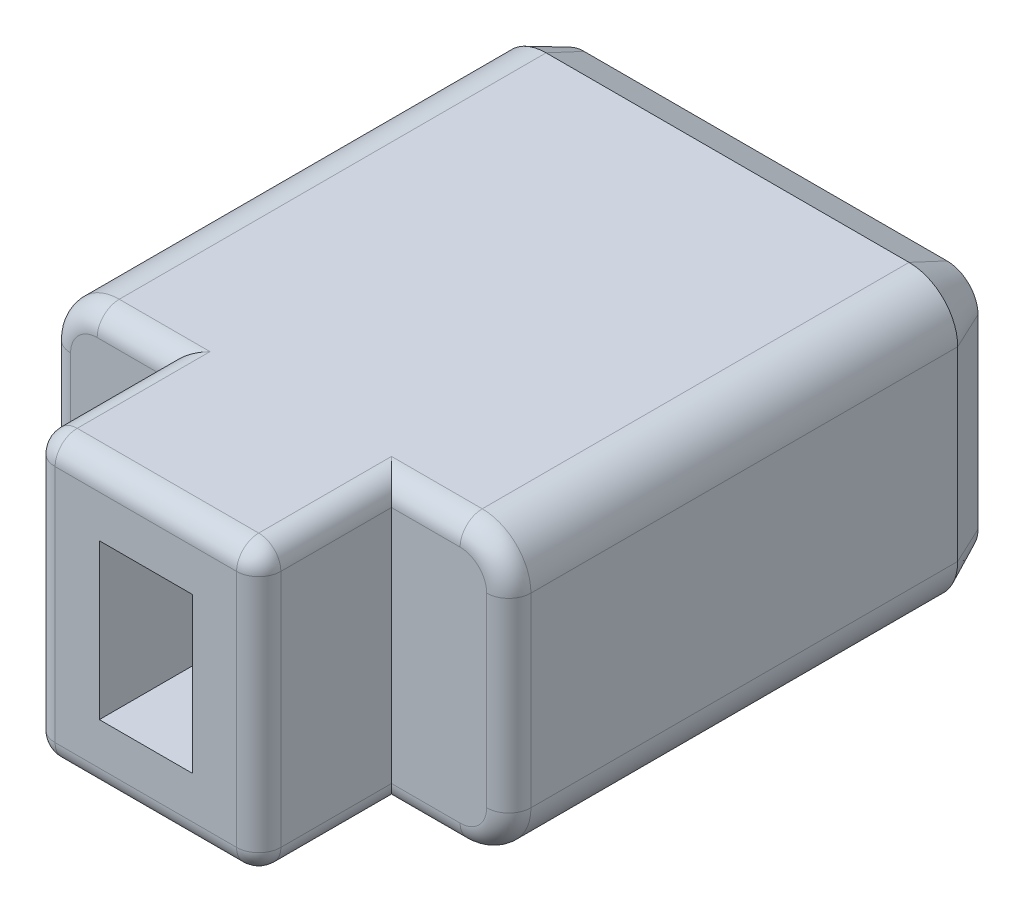
SolidWorks part; units mm, degrees
ref_plane "Plan de face" through (0, 0, 0) normal (0, 0, 1) x (1, 0, 0)
ref_plane "Plan de dessus" through (0, 0, 0) normal (0, 1, 0) x (1, 0, 0)
ref_plane "Plan de droite" through (0, 0, 0) normal (1, 0, 0) x (0, 0, -1)
sketch "Esquisse2" plane through (0, 0, 0) normal (0, 0, 1) x (1, 0, 0)
  line L1 (1.1, 0) -> (9.3, 0)
  line L2 (0, 1.1) -> (0, 5.3)
  line L3 (1.1, 6.4) -> (9.3, 6.4)
  line L4 (10.4, 1.1) -> (10.4, 5.3)
  arc A0 (9.3, 6.4) -> (10.4, 5.3) centre (9.3, 5.3) cw
  arc A1 (9.3, 0) -> (10.4, 1.1) centre (9.3, 1.1) ccw
  arc A2 (1.1, 0) -> (0, 1.1) centre (1.1, 1.1) cw
  arc A3 (0, 5.3) -> (1.1, 6.4) centre (1.1, 5.3) cw
  point P7 (10.4, 6.4)
  point P12 (0, 0)
  point P15 (0, 6.4)
  dimension "D3" = 1.1
  dimension "D1" = 10.4
  dimension "D2" = 6.4
extrude "Boss.-Extru.1" add sketch "Esquisse2" along normal blind 14
sketch "Esquisse3" plane through (0, 0, 14) normal (0, 0, 1) x (1, 0, 0)
  line L0 (0, 5.3) -> (0, 1.1) construction
  line L1 (4.15, 4.95) -> (6.25, 4.95)
  line L2 (4.15, 4.95) -> (4.15, 1.45)
  line L3 (4.15, 1.45) -> (6.25, 1.45)
  line L4 (6.25, 4.95) -> (6.25, 1.45)
  line L5 (10.4, 1.1) -> (10.4, 5.3) construction
  line L6 (9.3, 6.4) -> (1.1, 6.4) construction
  line L7 (1.1, 0) -> (9.3, 0) construction
  dimension "D1" = 2.1
  dimension "D2" = 3.5
  dimension "D3" = 4.15
  dimension "D4" = 4.15
  dimension "D5" = 1.45
  dimension "D6" = 1.45
extrude "Enlèv. mat.-Extru.1" cut sketch "Esquisse3" against normal blind 3
sketch "Esquisse4" plane through (0, 0, 14) normal (0, 0, 1) x (1, 0, 0)
  line L0 (2.65, 6.4) -> (2.65, 0)
  line L1 (9.3, 6.4) -> (1.1, 6.4) construction
  line L2 (1.1, 0) -> (9.3, 0) construction
  line L3 (2.65, 0) -> (7.75, 0)
  line L4 (7.75, 0) -> (7.75, 6.4)
  line L5 (7.75, 6.4) -> (2.65, 6.4)
  line L6 (4.15, 4.95) -> (4.15, 1.45) construction
  line L7 (6.25, 1.45) -> (6.25, 4.95) construction
  dimension "D1" = 1.5
  dimension "D2" = 1.5
extrude "Enlèv. mat.-Extru.2" cut sketch "Esquisse4" against normal blind 3 flip side to cut
fillet "Congé1" radius 0.5 18 edges at (8.525, 0, 11) (10.0778, 0.3222, 11) (10.4, 3.2, 11) (10.0778, 6.0778, 11) (1.875, 6.4, 11) (0.3222, 6.0778, 11) (1.875, 0, 11) (0.3222, 0.3222, 11) (7.75, 6.4, 12.5) (2.65, 6.4, 12.5) (7.75, 0, 12.5) (2.65, 0, 12.5) (2.65, 3.2, 14) (5.2, 6.4, 14) (7.75, 3.2, 14) (5.2, 0, 14) (8.525, 6.4, 11) (0, 3.2, 11)
chamfer "Chanfrein1" distance 0.4 angle 65 8 edges at (5.2, 0, 0) (10.0778, 0.3222, 0) (0.3222, 0.3222, 0) (10.4, 3.2, 0) (0, 3.2, 0) (10.0778, 6.0778, 0) (0.3222, 6.0778, 0) (5.2, 6.4, 0) first distance on face at (5.2, 3.2, 0)
sketch "Esquisse5" plane through (0, 0, 0) normal (0, 0, -1) x (-1, 0, 0)
  line L0 (-0.4, 5.3) -> (-10, 5.3) construction
  arc A0 (-9.3, 6) -> (-10, 5.3) centre (-9.3, 5.3) ccw construction
  text T0 "CLR" font "Century Gothic" height 4
extrude "Enlèv. mat.-Extru.3" cut sketch "Esquisse5" against normal blind 0.3
extrude "Boss.-Extru.2" add sketch "Esquisse5<2>" along normal blind 0.3 separate body
sketch "Esquisse5<2>" plane through (0, 0, 0) normal (0, 0, -1) x (-1, 0, 0) same geometry as "Esquisse5"
